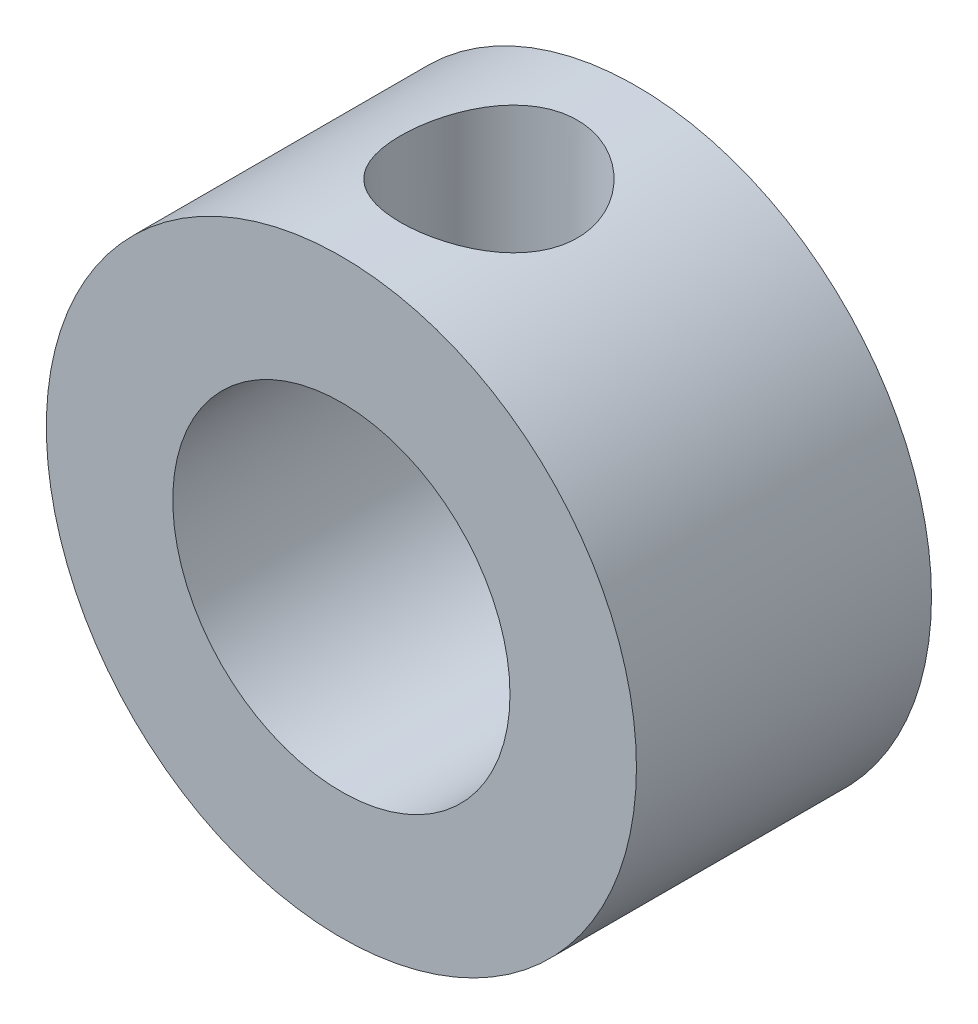
SolidWorks part; units mm, degrees
material "Plain Carbon Steel"
ref_plane "Front Plane" through (0, 0, 0) normal (0, 0, 1) x (1, 0, 0)
ref_plane "Top Plane" through (0, 0, 0) normal (0, 1, 0) x (1, 0, 0)
ref_plane "Right Plane" through (0, 0, 0) normal (1, 0, 0) x (0, 0, -1)
sketch "Sketch1" plane through (0, 0, 0) normal (0, 0, 1) x (1, 0, 0)
  circle A0 centre (0, 0) radius 4
  circle A1 centre (0, 0) radius 7
  dimension "D1" = 8
  dimension "D2" = 14
extrude "Boss-Extrude1" add sketch "Sketch1" along normal blind 7
ref_plane "Plane1" through (0, 7, 0) normal (0, 1, 0) x (1, 0, 0)
hole_wizard "M5x0.8 Tapped Hole1" positions "Sketch3" profile "Sketch2" tap size "M5x0.8" standard "ANSI Metric" end condition up to next
sketch "Sketch3" plane through (0, 7, 0) normal (0, 1, 0) x (1, 0, 0)
  line L0 (0, 0) -> (0, -7) construction
  line L1 (-7, -7) -> (7, -7) construction
  point P8 (0, -3.5)
sketch "Sketch2" plane through (0, 7, 3.5) normal (1, 0, 0) x (0, 0, 1)
  line L0 (0, 0) -> (0, 3)
  line L1 (0, 3) -> (2.1, 3)
  line L2 (2.1, 3) -> (2.1, 0)
  line L5 (2.1, 0) -> (0, 0)
  line L11 (0, -6.35) -> (0, 107.95) construction
  dimension "Thread Major Dia." = 4.2
  dimension "Thru Tap Drill Depth" = 3
